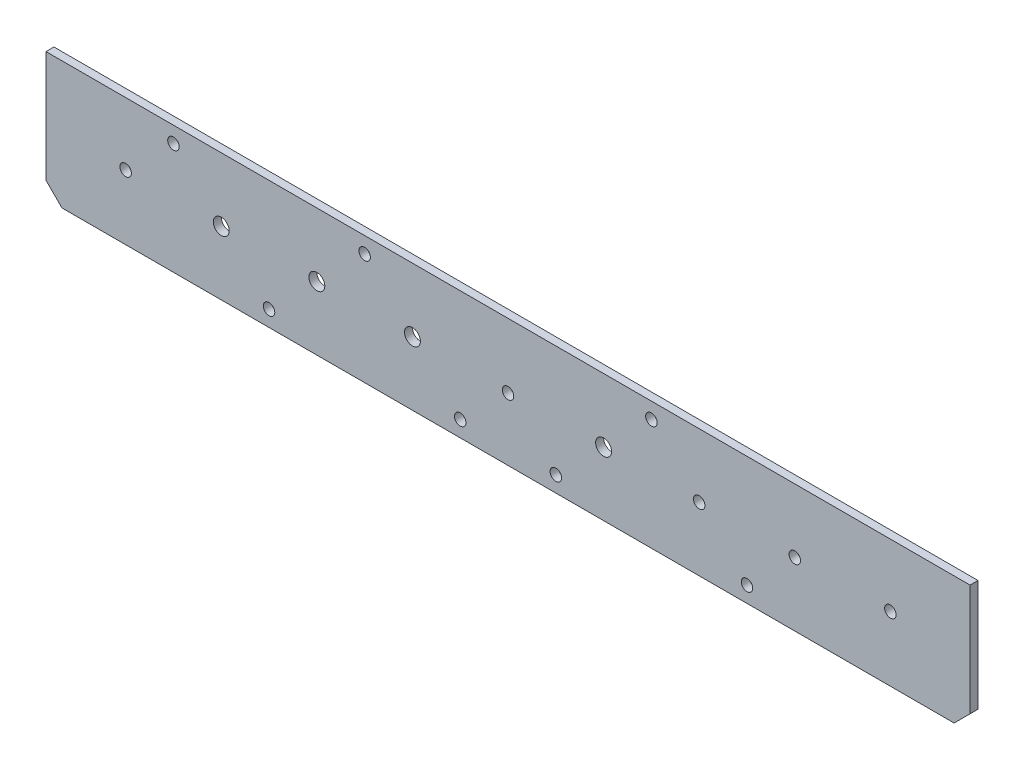
SolidWorks part; units mm, degrees
ref_plane "Front Plane" through (0, 0, 0) normal (0, 0, 1) x (1, 0, 0)
ref_plane "Top Plane" through (0, 0, 0) normal (0, 1, 0) x (1, 0, 0)
ref_plane "Right Plane" through (0, 0, 0) normal (1, 0, 0) x (0, 0, -1)
sketch "Sketch1" plane through (0, 0, 0) normal (0, 0, 1) x (1, 0, 0)
  line L1 (0, 0) -> (368.3, 0)
  line L2 (0, 0) -> (0, 50.8)
  line L3 (0, 50.8) -> (368.3, 50.8)
  line L4 (368.3, 0) -> (368.3, 50.8)
  dimension "D1" = 50.8
  dimension "D2" = 368.3
extrude "Boss-Extrude1" add sketch "Sketch1" along normal blind 3.175
sketch "Sketch2" plane through (0, 0, 3.175) normal (0, 0, 1) x (1, 0, 0)
  line L0 (184.15, 25.0031) -> (31.75, 25.7969) construction
  line L1 (184.15, 50.8) -> (184.15, 0) construction
  line L2 (368.3, 50.8) -> (0, 50.8) construction
  line L3 (0, 0) -> (368.3, 0) construction
  line L4 (184.15, 25.0031) -> (336.55, 25.7969) construction
  line L5 (0, 6.35) -> (0, 0)
  line L6 (0, 50.8) -> (0, 0) construction
  line L7 (0, 0) -> (6.35, 0)
  line L8 (6.35, 0) -> (0, 6.35)
  line L9 (368.3, 0) -> (361.95, 0)
  line L10 (361.95, 0) -> (368.3, 6.35)
  line L11 (368.3, 6.35) -> (368.3, 0)
  circle A0 centre (31.75, 25.7969) radius 2.286
  circle A1 centre (184.15, 25.0031) radius 2.286
  circle A2 centre (107.95, 25.4) radius 3.175
  circle A3 centre (69.85, 25.4) radius 3.175
  circle A4 centre (146.05, 25.4) radius 3.175
  circle A5 centre (222.25, 25.4) radius 3.175
  circle A6 centre (298.45, 25.4) radius 2.286
  circle A7 centre (260.35, 25.4) radius 2.286
  circle A8 centre (336.55, 25.7969) radius 2.286
  circle A9 centre (50.8, 44.45) radius 2.286
  circle A10 centre (165.1, 6.35) radius 2.286
  circle A11 centre (203.2, 6.35) radius 2.286
  circle A13 centre (127, 44.45) radius 2.286
  circle A14 centre (241.3, 44.45) radius 2.286
  circle A15 centre (88.9, 6.35) radius 2.286
  circle A16 centre (279.4, 6.35) radius 2.286
  point P17 (184.15, 25.4)
  dimension "D2" = 4.572
  dimension "D5" = 6.35
  dimension "D7" = 4.572
  dimension "D12" = 4.572
  dimension "D15" = 4.572
  dimension "D16" = 4.572
  dimension "D19" = 4.572
  dimension "D21" = 6.35
  dimension "D1" = 0.7937
  dimension "D3" = 38.1
  dimension "D4" = 152.4
  dimension "D6" = 38.1
  dimension "D8" = 57.15
  dimension "D9" = 19.05
  dimension "D10" = 57.15
  dimension "D11" = 19.05
  dimension "D13" = 57.15
  dimension "D14" = 19.05
  dimension "D17" = 19.05
  dimension "D18" = 19.05
  dimension "D20" = 19.05
  dimension "D22" = 6.35
extrude "Cut-Extrude1" cut sketch "Sketch2" against normal up to next
